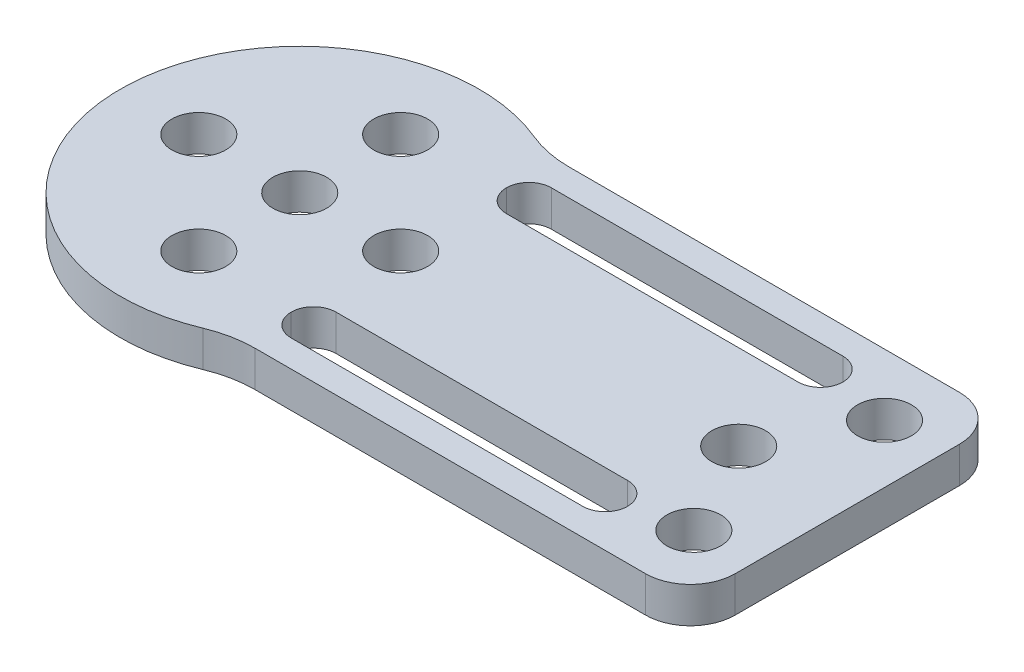
SolidWorks part; units mm, degrees
ref_plane "Front Plane" through (0, 0, 0) normal (0, 0, 1) x (1, 0, 0)
ref_plane "Top Plane" through (0, 0, 0) normal (0, 1, 0) x (1, 0, 0)
ref_plane "Right Plane" through (0, 0, 0) normal (1, 0, 0) x (0, 0, -1)
sketch "Sketch1" plane through (0, 0, 0) normal (0, 1, 0) x (1, 0, 0)
  line L0 (-12.7, 0) -> (12.7, 0) construction
  line L1 (-12.7, -7) -> (12.7, -7) construction
  line L2 (-12.7, 7) -> (12.7, 7) construction
  line L3 (11.7164, 7) -> (-8.827, 7)
  line L4 (-8.827, -7) -> (11.7164, -7)
  line L5 (11.7164, -7) -> (11.7164, 7)
  arc A0 (-8.827, 7) -> (-8.827, -7) centre (-12.7, 0) ccw
  circle A1 centre (-12.7, 0) radius 25.4 construction
  point P3 (0, 0)
  dimension "D1" = 50.8
  dimension "D2" = 16
  dimension "D3" = 7
  dimension "D4" = 7
extrude "Boss-Extrude1" add sketch "Sketch1" along normal mid plane 1.6
fillet "Fillet1" radius 2 2 edges at (11.7164, 0, -7) (11.7164, 0, 7)
fillet "Fillet2" radius 5 2 edges at (-8.827, 0, -7) (-8.827, 0, 7)
sketch "Sketch2" plane through (0, 0.8, 0) normal (0, 1, 0) x (1, 0, 0)
  circle A0 centre (-12.7, 0) radius 4.5 construction
  circle A1 centre (-8.2, 0) radius 1.2
  circle A2 centre (-12.7, 4.5) radius 1.2
  circle A3 centre (-17.2, 0) radius 1.2
  circle A4 centre (-12.7, -4.5) radius 1.2
  circle A5 centre (-12.7, 0) radius 1.2
  dimension "D1" = 2.4
  dimension "D2" = 9
extrude "Cut-Extrude1" cut sketch "Sketch2" against normal through all
sketch "Sketch3" plane through (0, 0.8, 0) normal (0, 1, 0) x (1, 0, 0)
  line L0 (9.1214, 4.25) -> (9.1214, -4.25) construction
  line L1 (9.1214, -4.25) -> (6.8714, 0) construction
  line L2 (6.8714, 0) -> (9.1214, 4.25) construction
  line L3 (11.7164, -5) -> (11.7164, 5) construction
  circle A0 centre (9.1214, 4.25) radius 1.2
  circle A1 centre (9.1214, -4.25) radius 1.2
  circle A2 centre (6.8714, 0) radius 1.2
  dimension "D1" = 2.4
  dimension "D2" = 2.25
  dimension "D3" = 4.25
  dimension "D4" = 2.595
extrude "Cut-Extrude2" cut sketch "Sketch3" against normal through all
sketch "Sketch4" plane through (0, 0.8, 0) normal (0, 1, 0) x (1, 0, 0)
  circle A0 centre (9.1214, 4.25) radius 2.2 construction
  circle A1 centre (6.8714, 0) radius 2.2 construction
  circle A2 centre (9.1214, -4.25) radius 2.2 construction
  dimension "D1" = 4.4
sketch "Sketch5" plane through (0, 0.8, 0) normal (0, 1, 0) x (1, 0, 0)
  line L0 (-7.7, -7) -> (9.7164, -7) construction
  line L1 (-8.2836, 5.8) -> (6.7164, 5.8)
  line L2 (-8.2836, 5.8) -> (-8.2836, 3.8)
  line L3 (-8.2836, 3.8) -> (6.7164, 3.8)
  line L4 (6.7164, 5.8) -> (6.7164, 3.8)
  line L5 (-8.2836, -3.8) -> (6.7164, -3.8)
  line L6 (-8.2836, -3.8) -> (-8.2836, -5.8)
  line L7 (-8.2836, -5.8) -> (6.7164, -5.8)
  line L8 (6.7164, -3.8) -> (6.7164, -5.8)
  line L9 (9.7164, 7) -> (-7.7, 7) construction
  line L10 (11.7164, -5) -> (11.7164, 5) construction
  dimension "D1" = 1.2
  dimension "D2" = 1.2
  dimension "D3" = 15
  dimension "D4" = 15
  dimension "D5" = 5
  dimension "D6" = 5
  dimension "D7" = 2
  dimension "D8" = 2
extrude "Cut-Extrude3" cut sketch "Sketch5" against normal through all
fillet "Fillet3" radius 1 8 edges at (-8.2836, 0, 5.8) (6.7164, 0, 5.8) (6.7164, 0, 3.8) (-8.2836, 0, 3.8) (-8.2836, 0, -3.8) (6.7164, 0, -3.8) (6.7164, 0, -5.8) (-8.2836, 0, -5.8)
equation "\"D4@Sketch3\"=(7.44-\"D2@Sketch3\")/2"
